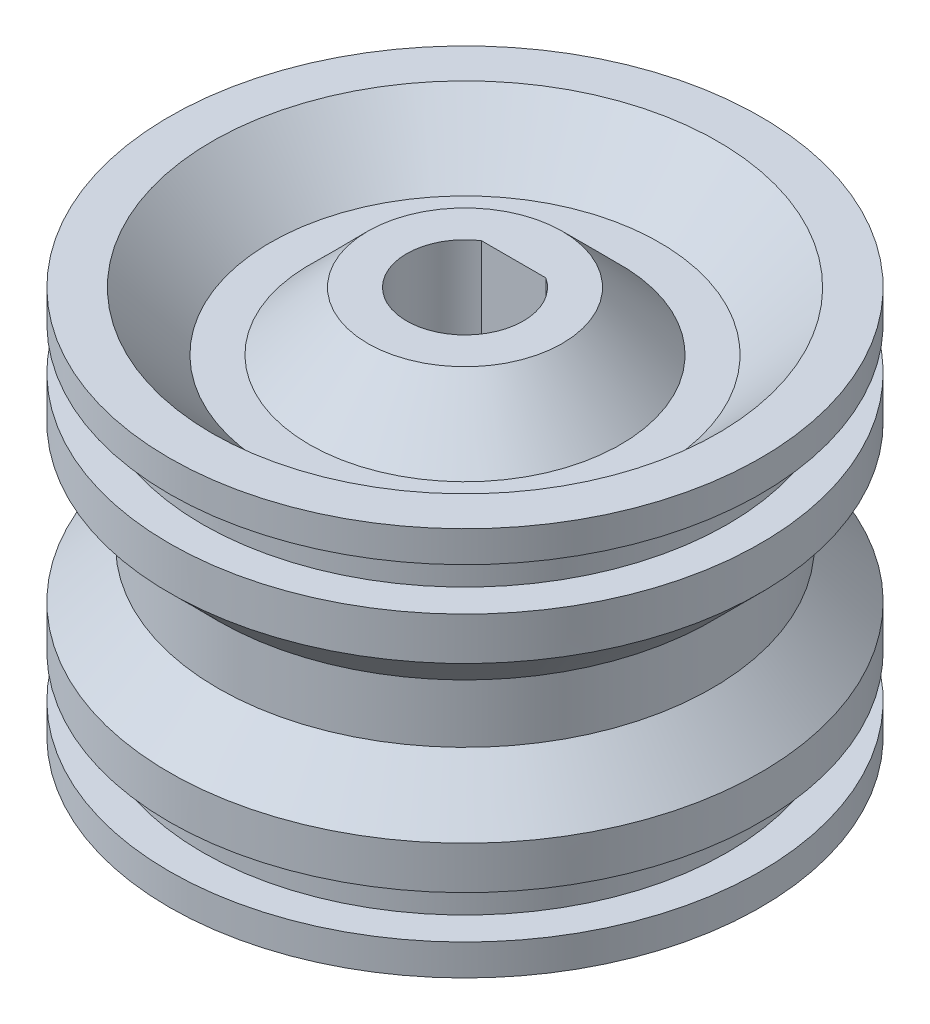
SolidWorks part; units mm, degrees
ref_plane "前视基准面" through (0, 0, 0) normal (0, 0, 1) x (1, 0, 0)
ref_plane "上视基准面" through (0, 0, 0) normal (0, 1, 0) x (1, 0, 0)
ref_plane "右视基准面" through (0, 0, 0) normal (1, 0, 0) x (0, 0, -1)
other "Configuration Table"
sketch "草图1" plane through (0, 0, 0) normal (0, 1, 0) x (1, 0, 0)
  circle A0 centre (0, 0) radius 15.2
  dimension "D1" = 30.4
extrude "凸台-拉伸1" add sketch "草图1" along normal mid plane 20
sketch "草图2" plane through (0, 0, 0) normal (0, 0, 1) x (1, 0, 0)
  line L0 (15.2, -10) -> (15.2, 10) construction
  line L1 (15.2, 8.4) -> (0, 8.4) construction
  line L2 (15.2, 8.4) -> (15.2, 6.2) construction
  line L3 (15.2, 6.2) -> (0, 6.2) construction
  line L4 (0, 8.4) -> (0, 6.2) construction
  line L5 (15.2, 10) -> (-15.2, 10) construction
  line L7 (15.2, 8.4) -> (13.5, 8.4)
  line L8 (15.2, 8.4) -> (15.2, 6.2)
  line L9 (15.2, 6.2) -> (13.5, 6.2)
  line L10 (13.5, 8.4) -> (13.5, 6.2)
  dimension "D1" = 2.2
  dimension "D2" = 1.6
  dimension "D3" = 1.7
revolve "切除-旋转1" cut sketch "草图2" angle 360 about L4
mirror "镜向1" about plane through (0, 0, 0) normal (0, 1, 0) of "切除-旋转1"
sketch "草图4" plane through (0, -10, 0) normal (0, -1, 0) x (1, 0, 0)
  circle A0 centre (0, 0) radius 10
  dimension "D1" = 20
extrude "切除-拉伸1" cut sketch "草图4" against normal blind 12
sketch "草图5" plane through (0, 10, 0) normal (0, 1, 0) x (1, 0, 0)
  line L0 (-1.6583, 2.5) -> (1.6583, 2.5)
  circle A0 centre (0, 0) radius 3
  dimension "D1" = 6
  dimension "D2" = 2.5
extrude "切除-拉伸2" cut sketch "草图5" against normal blind 15 contours L0 A0 region at (0, 10, 0.112)
chamfer "倒角1" distance 3 angle 45 1 edges at (0, -10, -10)
sketch "草图6" plane through (0, 10, 0) normal (0, 1, 0) x (1, 0, 0)
  circle A0 centre (0, 0) radius 5
  circle A1 centre (0, 0) radius 10
  dimension "D1" = 20
  dimension "D2" = 10
extrude "切除-拉伸3" cut sketch "草图6" against normal blind 3
chamfer "倒角2" distance 3 angle 45 2 edges at (0, 7, 5) (0, 10, 10)
sketch "草图7" plane through (0, 0, 0) normal (1, 0, 0) x (0, 0, -1)
  line L0 (15.2, -6.2) -> (15.2, 6.2) construction
  line L1 (12.7, -4) -> (15.2, -4)
  line L2 (12.7, -4) -> (12.7, 4)
  line L3 (12.7, 4) -> (15.2, 4)
  line L4 (15.2, -4) -> (15.2, 4)
  line L5 (12.7, -4) -> (15.2, 4) construction
  line L6 (12.7, 4) -> (15.2, -4) construction
  point P0 (13.95, 0)
  point P7 (0, 0)
  dimension "D1" = 2.5
  dimension "D2" = 8
ref_axis "基准轴1" through (0, 2, 0) along (0, 1, 0)
revolve "切除-旋转2" cut sketch "草图7" angle 360 about axis through (0, 2, 0) along (0, 1, 0)
chamfer "倒角3" distance 2.5 angle 45 2 edges at (0, 4, -12.7) (0, -4, -12.7)
